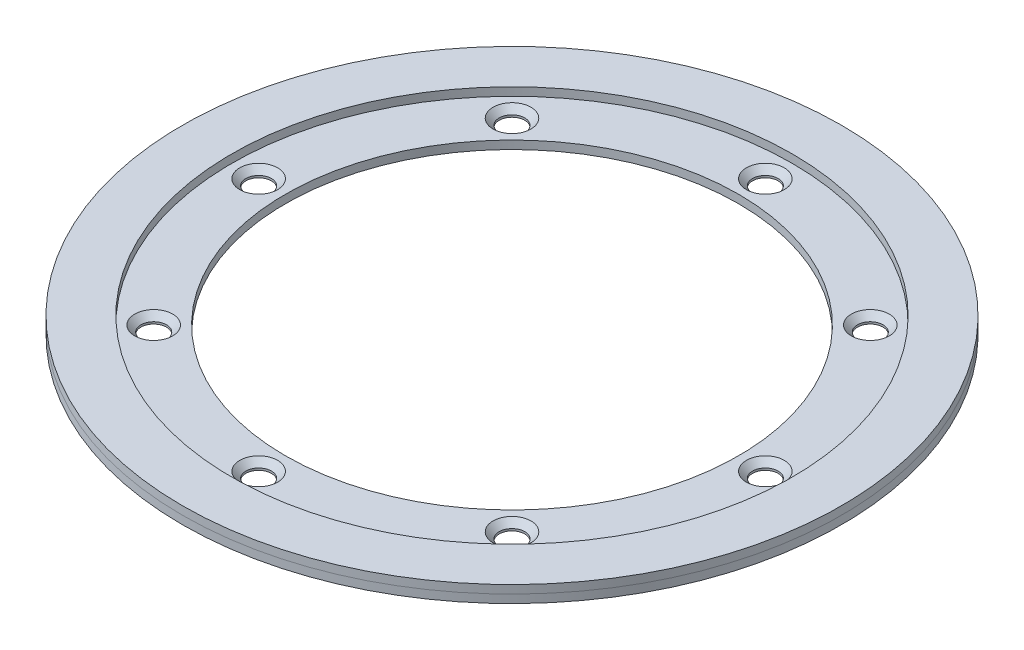
SolidWorks part; units mm, degrees
ref_plane "Front Plane" through (0, 0, 0) normal (0, 0, 1) x (1, 0, 0)
ref_plane "Top Plane" through (0, 0, 0) normal (0, 1, 0) x (1, 0, 0)
ref_plane "Right Plane" through (0, 0, 0) normal (1, 0, 0) x (0, 0, -1)
sketch "Sketch1" plane through (0, 0, 0) normal (0, 0, 1) x (1, 0, 0)
  line L0 (0, 0) -> (0, 12.8097) construction
  line L1 (-40, 0) -> (-27.5, 0)
  line L2 (-40, 0) -> (-40, 2)
  line L3 (-40, 2) -> (-34, 2)
  line L4 (-27.5, 0) -> (-27.5, 1)
  line L7 (-34, 2) -> (-34, 1)
  line L8 (-34, 1) -> (-27.5, 1)
  dimension "D1" = 80
  dimension "D2" = 55
  dimension "D3" = 2
  dimension "D4" = 1
  dimension "D5" = 68
revolve "Revolve1" add sketch "Sketch1" angle 360 about L0
hole_wizard "CSK for M2.5 Countersunk Flat Head Screw1" positions "Sketch3" profile "Sketch2" countersink size "M2.5" standard "DIN" end condition through all
sketch "Sketch3" plane through (0, 1, 0) normal (0, 1, 0) x (1, 0, 0)
  point P0 (0, 30.75)
  dimension "D1" = 30.75
sketch "Sketch2" plane through (0, 1, -30.75) normal (1, 0, 0) x (0, 0, 1)
  line L0 (0, 0) -> (0, 1)
  line L1 (0, 1) -> (1.55, 1)
  line L2 (1.55, 1) -> (1.55, 0.75)
  line L3 (1.55, 0.75) -> (2.3, 0)
  line L5 (2.3, 0) -> (0, 0)
  line L6 (-1.55, 0.75) -> (-2.3, 0) construction
  line L11 (0, -6.35) -> (0, 107.95) construction
  dimension "Thru Hole Dia." = 3.1
  dimension "Thru Hole Depth" = 1
  dimension "Near C'Sink Dia." = 4.6
  dimension "Near C'Sink Angle" = 90
pattern_circular "CirPattern1" count 8 over 360 about axis through (0, 1, 0) along (0, -1, 0) of "CSK for M2.5 Countersunk Flat Head Screw1"
sketch "Sketch4" plane through (0, 2, 0) normal (0, 1, 0) x (1, 0, 0)
  line L0 (-5.4607, -35.0278) -> (-2.5377, -35.0277)
  line L1 (-5.6623, -35.2294) -> (-5.6623, -38.0744)
  line L2 (5.5909, -35.0277) -> (5.6963, -35.0277)
  line L3 (-5.4607, -38.276) -> (-2.5377, -38.276)
  line L4 (-2.3361, -35.2293) -> (-2.3361, -38.0744)
  line L5 (-1.6872, -35.0277) -> (-1.6872, -38.276)
  line L6 (-0.5439, -38.276) -> (-0.5439, -37.197)
  line L7 (-0.5439, -37.197) -> (0.0337, -38.276)
  line L8 (0.462, -36.9465) -> (1.3375, -38.276)
  line L9 (-0.1319, -35.0277) -> (-1.6872, -35.0277)
  line L10 (1.5654, -35.0277) -> (1.5654, -38.276)
  line L11 (2.7275, -37.2194) -> (3.8636, -37.2194)
  line L12 (3.8636, -37.2194) -> (3.8636, -38.276)
  line L13 (2.7275, -37.2194) -> (2.7275, -35.0277)
  line L14 (4.4733, -37.0675) -> (4.0988, -37.9277)
  line L15 (6.7188, -35.3154) -> (6.3674, -36.1227)
  line L16 (5.3046, -38.276) -> (5.4254, -38.276)
  line L17 (1.5654, -38.276) -> (3.8636, -38.276)
  line L18 (1.5654, -35.0277) -> (2.7275, -35.0277)
  line L19 (0.0337, -38.276) -> (1.3375, -38.276)
  line L20 (-1.6872, -38.276) -> (-0.5439, -38.276)
  line L21 (-1.6872, -35.0277) -> (-0.1319, -35.0277)
  line L22 (-4.8679, -37.2883) -> (-4.5364, -37.6293)
  line L23 (-4.5364, -37.6293) -> (-4.6748, -37.7638)
  line L24 (-4.42, -38.0216) -> (-2.5916, -36.1842)
  line L25 (-2.838, -35.939) -> (-2.9741, -36.0757)
  line L26 (-2.9741, -36.0757) -> (-3.3112, -35.7403)
  line L27 (-0.5439, -35.8658) -> (-0.5439, -36.4946)
  line L28 (-0.5439, -36.4946) -> (-0.3159, -36.4946)
  line L29 (-0.3159, -35.8658) -> (-0.5439, -35.8658)
  line L30 (-5.6623, -35.0278) -> (0.5282, -35.0277) construction
  line L31 (0.5282, -35.0277) -> (6.7188, -35.0277) construction
  line L32 (6.7188, -35.3154) -> (6.7188, -35.0277) construction
  arc A0 (-3.3112, -35.7403) -> (-4.8679, -37.2883) centre (-4.0808, -36.5231) ccw
  arc A1 (-4.6748, -37.7638) -> (-4.42, -38.0216) centre (-4.5485, -37.8938) ccw
  arc A2 (-2.5916, -36.1842) -> (-2.838, -35.939) centre (-2.7148, -36.0616) ccw
  arc A3 (-5.6623, -38.0744) -> (-5.4607, -38.276) centre (-5.4607, -38.0744) ccw
  arc A4 (-2.3361, -38.0744) -> (-2.5377, -38.276) centre (-2.5377, -38.0744) cw
  arc A5 (-2.3361, -35.2293) -> (-2.5377, -35.0277) centre (-2.5377, -35.2293) ccw
  arc A6 (-5.6623, -35.2294) -> (-5.4607, -35.0278) centre (-5.4607, -35.2294) cw
  arc A7 (-0.3159, -36.4946) -> (-0.3159, -35.8658) centre (-0.3159, -36.1802) ccw
  spline S0 degree 3 poles (0.462, -36.9465) (0.7517, -36.9107) (1.1341, -36.545) (1.1014, -35.5488) (0.5739, -35.1352) (0.0229, -35.0277) (-0.1319, -35.0277) knots 0 0 0 0 0.237341 0.494881 0.818681 1 1 1 1
  spline S1 degree 3 poles (6.7188, -35.3154) (6.4509, -35.1637) (5.9992, -35.015) (5.2645, -35.0361) (4.9411, -35.1332) (4.2602, -35.6109) (4.1501, -36.4985) (4.6955, -36.8881) (5.1277, -37.0351) (5.3063, -37.0185) (5.5658, -37.1591) (5.5053, -37.3656) (5.2714, -37.4071) (4.8574, -37.3112) (4.6921, -37.2011) (4.4733, -37.0675) knots 0 0 0 0 0.124331 0.150635 0.25055 0.282174 0.454388 0.523889 0.544131 0.656805 0.734227 0.751935 0.824785 0.850502 1 1 1 1
  spline S2 degree 3 poles (6.3674, -36.1227) (6.2198, -36.0124) (6.0552, -35.9184) (5.6173, -35.8491) (5.4429, -35.9438) (5.4426, -36.1052) (5.8663, -36.2745) (6.2253, -36.2926) (6.7372, -36.6644) (6.8291, -37.1357) (6.5991, -37.8122) (6.2171, -38.1248) (5.6512, -38.2528) (5.4067, -38.2873) (4.8963, -38.2392) (4.5528, -38.1276) (4.0988, -37.9277) knots 0 0 0 0 0.063502 0.104188 0.136084 0.143538 0.178722 0.283871 0.315411 0.474261 0.517196 0.701825 0.732305 0.791516 0.819025 1 1 1 1
extrude "Cut-Extrude1" [suppressed] cut sketch "Sketch4" against normal blind 0.1 contours A6 L1 A3 L3 A4 L4 A5 L0 A2 L24 A1 L23 L22 A0 L26 L25 | L8 S0 L9 L5 L20 L6 L7 L19 A7 L28 L27 L29 | L18 L10 L17 L12 L11 L13 | S2 L15 S1 L2 L14 L16
sketch "Sketch5" plane through (0, 2, 0) normal (0, 1, 0) x (1, 0, 0)
  arc A0 (-27.032, 22.2322) -> (-27.032, -22.2322) centre (0, 0) ccw construction
  circle A1 centre (0, 0) radius 34 construction
  text T0 "MR080N055B122A00"
  dimension "D1" = 35
extrude "Cut-Extrude2" [suppressed] cut sketch "Sketch5" against normal blind 0.1
sketch "Sketch6" plane through (0, 2, 0) normal (0, 1, 0) x (1, 0, 0)
  arc A0 (29.6207, 18.6444) -> (29.6207, -18.6444) centre (0, 0) cw construction
  circle A1 centre (0, 0) radius 34 construction
  text T0 "Ser.No.:######"
  dimension "D1" = 35
extrude "Cut-Extrude3" [suppressed] cut sketch "Sketch6" against normal blind 0.1
split "Split1" bodies to split 103 resulting bodies 107 108 split by face at (-21.7435, 1, -19.4435)
